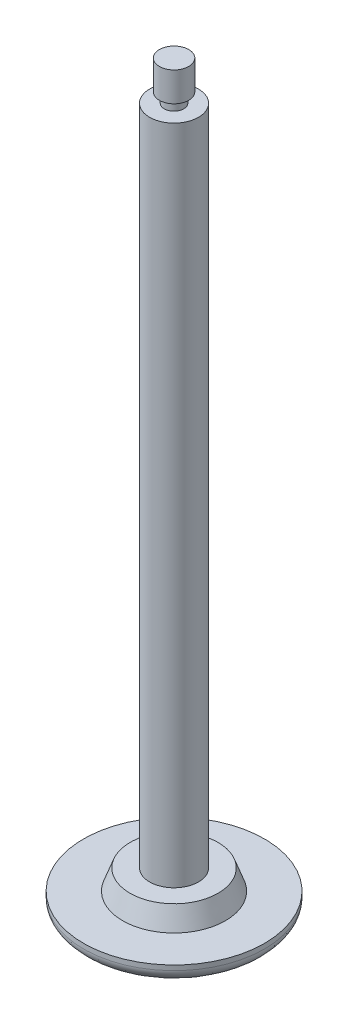
SolidWorks part; units mm, degrees
material "Plain Carbon Steel"
ref_plane "Front Plane" through (0, 0, 0) normal (0, 0, 1) x (1, 0, 0)
ref_plane "Top Plane" through (0, 0, 0) normal (0, 1, 0) x (1, 0, 0)
ref_plane "Right Plane" through (0, 0, 0) normal (1, 0, 0) x (0, 0, -1)
sketch "Sketch1" plane through (0, 0, 0) normal (0, 0, 1) x (1, 0, 0)
  line L0 (0, 0) -> (0, 155.5) construction
  line L1 (0, 0) -> (0, 1) construction
  line L2 (18.5, 7) -> (18.5, 8)
  line L3 (18.5, 8) -> (10.5, 8)
  line L7 (3, 155.5) -> (0, 155.5)
  line L8 (0, 155.5) -> (0, 1)
  line L12 (9, 12.1212) -> (10.5, 8)
  line L13 (2, 147.5) -> (2, 149.5)
  line L14 (2, 149.5) -> (3, 149.5)
  line L15 (3, 149.5) -> (3, 155.5)
  line L17 (0, -5.5) -> (0, -7.5334) construction
  line L18 (2, 147.5) -> (5, 147.5)
  line L19 (5, 147.5) -> (5, 12.1212)
  line L20 (5, 12.1212) -> (9, 12.1212)
  ellipse E0 centre (0, 7) end of major axis (18.5, 7) minor radius 6 (0, 1) -> (18.5, 7) ccw
  point P17 (2, 101.7926)
  point P22 (2, 106.125)
  point P23 (0, 0)
  point P24 (0, 16.2548)
  dimension "D2" = 10
  dimension "D3" = 7
  dimension "D4" = 21
  dimension "D5" = 6
  dimension "D6" = 18
  dimension "D7" = 110
  dimension "D8" = 146.5
  dimension "D9" = 2
  dimension "D10" = 6
  dimension "D11" = 37
  dimension "D12" = 6
  dimension "D13" = 4
  dimension "D14" = 1
revolve "Revolve1" add sketch "Sketch1" angle 360 about L0
ref_point "Apex"
